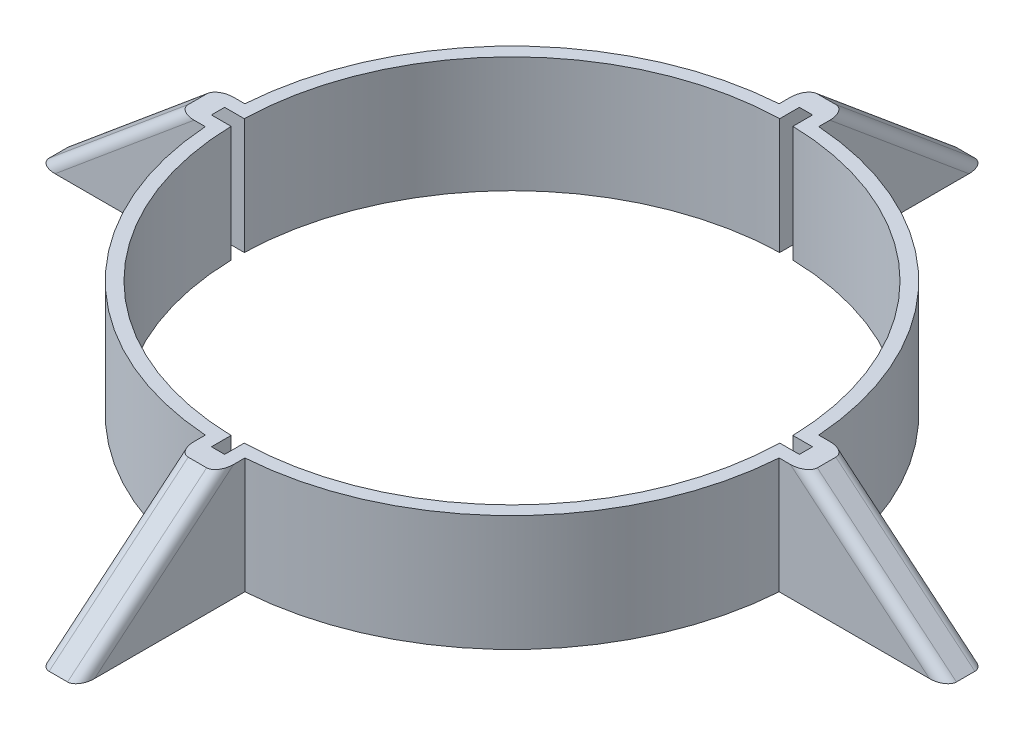
SolidWorks part; units mm, degrees
ref_plane "Front Plane" through (0, 0, 0) normal (0, 0, 1) x (1, 0, 0)
ref_plane "Top Plane" through (0, 0, 0) normal (0, 1, 0) x (1, 0, 0)
ref_plane "Right Plane" through (0, 0, 0) normal (1, 0, 0) x (0, 0, -1)
sketch "Sketch4" plane through (0, 0, 0) normal (0, 1, 0) x (1, 0, 0)
  circle A0 centre (0, 0) radius 69.215
  circle A1 centre (0, 0) radius 66.04
  dimension "D1" = 132.08
  dimension "D2" = 3.175
extrude "Boss-Extrude3" add sketch "Sketch4" along normal blind 114.3
sketch "Sketch7" plane through (0, 0, 0) normal (0, 0, 1) x (1, 0, 0)
  line L1 (69.215, 0) -> (69.215, 114.3) construction
  line L2 (55, 0) -> (-55, 0) construction
  line L4 (43.7827, 0.4093) -> (69.215, 0)
sketch "Sketch11" plane through (0, 0, 0) normal (0, 0, 1) x (1, 0, 0)
  line L5 (-1.5875, -101.6) -> (1.5875, -101.6)
  line L6 (-1.5875, -101.6) -> (-1.5875, 101.6)
  line L7 (-1.5875, 101.6) -> (1.5875, 101.6)
  line L8 (1.5875, -101.6) -> (1.5875, 101.6)
  line L9 (-1.5875, -101.6) -> (1.5875, 101.6) construction
  line L10 (-1.5875, 101.6) -> (1.5875, -101.6) construction
  point P0 (17.4909, 87.9422)
  point P1 (0, 0)
  dimension "D1" = 3.175
  dimension "D2" = 203.2
extrude "Cut-Extrude3" cut sketch "Sketch11" against normal up to surface and the other way through all up to face at (0, 114.3, 69.215)
sketch "Sketch12" plane through (0, 0, 0) normal (1, 0, 0) x (0, 0, -1)
  line L1 (1.5875, -101.6) -> (-1.5875, -101.6)
  line L2 (1.5875, -101.6) -> (1.5875, 101.6)
  line L3 (1.5875, 101.6) -> (-1.5875, 101.6)
  line L4 (-1.5875, -101.6) -> (-1.5875, 101.6)
  line L5 (1.5875, -101.6) -> (-1.5875, 101.6) construction
  line L6 (1.5875, 101.6) -> (-1.5875, -101.6) construction
  point P0 (0, 0)
  dimension "D1" = 3.175
  dimension "D2" = 203.2
extrude "Cut-Extrude4" cut sketch "Sketch12" against normal up to surface (69.1968 mm away) up to face at (0, 50.8, 0)
sketch "Sketch13" plane through (0, 0, 0) normal (1, 0, 0) x (0, 0, -1)
  line L1 (1.5875, -101.6) -> (-1.5875, -101.6)
  line L2 (1.5875, -101.6) -> (1.5875, 101.6)
  line L3 (1.5875, 101.6) -> (-1.5875, 101.6)
  line L4 (-1.5875, -101.6) -> (-1.5875, 101.6)
  line L5 (1.5875, -101.6) -> (-1.5875, 101.6) construction
  line L6 (1.5875, 101.6) -> (-1.5875, -101.6) construction
  point P0 (0, 0)
  dimension "D1" = 3.175
  dimension "D2" = 203.2
extrude "Cut-Extrude5" cut sketch "Sketch13" along normal up to surface (69.1968 mm away) up to face at (-19.6899, 50.8, 0)
ref_axis "Axis1" through (0, 0, 29.2768) along (0, 0, -1)
ref_axis "Axis2" through (-30.1352, 0, 0) along (1, 0, 0)
ref_plane "Plane2" through (69.215, 0, 0) normal (1, 0, 0) x (0, 0, -1)
sketch "Sketch16" plane through (69.215, 0, 0) normal (1, 0, 0) x (0, 0, -1)
  line L5 (0, 0) -> (0, 25.4)
  line L6 (-24.2888, 25.4) -> (28.8903, 25.4)
ref_plane "Plane1" through (28.3508, -23.6294, 0) normal (0.7682, -0.6402, 0) x (0, 0, -1)
sketch "Sketch17" plane through (28.3508, -23.6294, 0) normal (0.7682, -0.6402, 0) x (0, 0, -1)
  line L0 (-24.2888, 63.826) -> (28.8903, 63.826) construction
  line L1 (4.7625, 63.826) -> (-4.7625, 63.826)
  line L2 (4.7625, 63.826) -> (4.7625, 126.5528)
  line L3 (4.7625, 126.5528) -> (-4.7625, 126.5528)
  line L4 (-4.7625, 63.826) -> (-4.7625, 126.5528)
  line L5 (4.7625, 63.826) -> (-4.7625, 126.5528) construction
  line L6 (4.7625, 126.5528) -> (-4.7625, 63.826) construction
  point P0 (0, 95.1894)
  dimension "D1" = 62.7267
  dimension "D2" = 9.525
extrude "Boss-Extrude4" add sketch "Sketch17" against normal up to surface (0.2135 mm away) up to face at (0, 114.3, 69.215)
sketch "Sketch19" plane through (28.3508, -23.6294, 0) normal (0.7682, -0.6402, 0) x (0, 0, -1)
  line L0 (4.7625, 126.5528) -> (-4.7625, 126.5528) construction
  line L1 (-1.5875, 123.3778) -> (1.5875, 123.3778)
  line L2 (-1.5875, 123.3778) -> (-1.5875, 63.826)
  line L3 (-1.5875, 63.826) -> (1.5875, 63.826)
  line L4 (1.5875, 123.3778) -> (1.5875, 63.826)
  dimension "D1" = 3.175
  dimension "D2" = 3.175
extrude "Cut-Extrude6" cut sketch "Sketch19" against normal up to surface (53.7923 mm away) up to face at (0, 114.3, 66.04)
ref_axis "Axis3" through (0, -10.16, 0) along (0, 1, 0)
pattern_circular "CirPattern1" count 4 over 360 about axis through (0, -10.16, 0) along (0, 1, 0) of "Boss-Extrude4", "Cut-Extrude6"
fillet "Fillet2" radius 2.54 16 edges at (4.7625, 49.4925, -89.2952) (4.7625, 90.3894, -89.2132) (-4.7625, 49.4925, -89.2952) (-4.7625, 90.3894, -89.2132) (-89.2952, 49.4925, 4.7625) (-89.2952, 49.4925, -4.7625) (-89.2132, 90.3894, -4.7625) (-89.2132, 90.3894, 4.7625) (4.7625, 49.4925, 89.2952) (-4.7625, 49.4925, 89.2952) (-4.7625, 90.3894, 89.2132) (4.7625, 90.3894, 89.2132) (89.2132, 90.3894, -4.7625) (89.2132, 90.3894, 4.7625) (89.2952, 49.4925, 4.7625) (89.2952, 49.4925, -4.7625)
sketch "Sketch21" plane through (0, 0, 0) normal (1, 0, 0) x (0, 0, -1)
  line L1 (-135.0302, 119.9109) -> (140.5598, 119.9109)
  line L2 (-135.0302, 119.9109) -> (-135.0302, 101.6478)
  line L3 (-135.0302, 101.6478) -> (140.5598, 101.6478)
  line L4 (140.5598, 119.9109) -> (140.5598, 101.6478)
  line L5 (-135.0302, 73.7468) -> (140.5598, 73.7468)
  line L6 (-135.0302, 73.7468) -> (-135.0302, -1.072)
  line L7 (-135.0302, -1.072) -> (140.5598, -1.072)
  line L8 (140.5598, 73.7468) -> (140.5598, -1.072)
extrude "Cut-Extrude9" cut sketch "Sketch21" against normal through all both and the other way through all contours L2 L1 L4 L3 | L6 L5 L8 L7
equation "\"AIRFRAME_OD\"= 5.15in"
equation "\"AIRFRAME_ID\"= 4.99in"
equation "\"FLAT_T\"= 0.125in"
equation "\"COUPLER_OD\"= 4.998in"
equation "\"COUPLER_ID\"= 4.85in"
equation "\"NOSE_EXP_L\"= 27in"
equation "\"NOSE_SHOULDER_L\"= 5in"
equation "\"MAIN_L\"= 30in"
equation "\"RECO_COUP_L\"= 10in"
equation "\"RECO_SWITCH_L\"= 2in"
equation "\"RECO_ROD_X\"= 3.5in"
equation "\"DROGUE_L\"= 20in"
equation "\"ATS_FORE_COUP_L\"= 5.5in"
equation "\"ATS_AFT_COUP_L\"= 4.5in"
equation "\"ATS_ROD_X\"= 3.75in"
equation "\"LOWER_L\"= 30in"
equation "\"FIN_ROOT\"= 8in"
equation "\"FIN_X\"= 0.75in"
equation "\"FIN_N\"= 4"
equation "\"MOTOR_OD\"= 3.091in"
equation "\"MOTOR_ID\"= 3.00in"
equation "\"MOTOR_L\"= 14in"
equation "\"CR_AFT_X\"= 0.5in"
equation "\"CR_FORE_X\"= 9.25in"
equation "\"MOTOR_LOWER_X\"= 2in"
